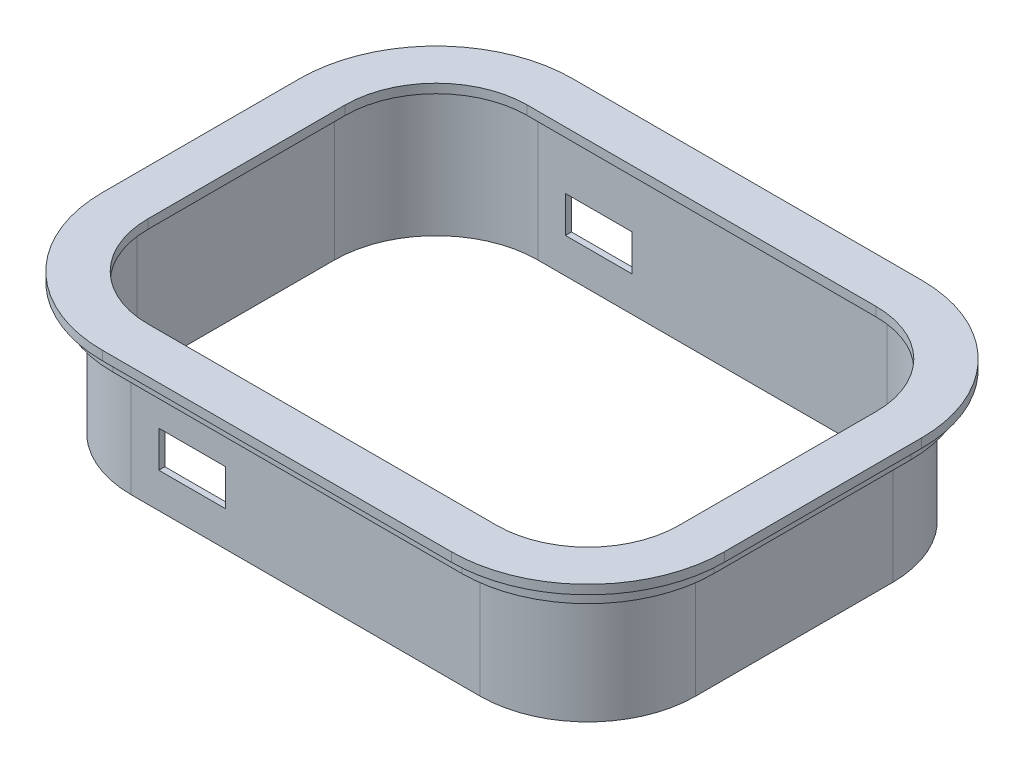
SolidWorks part; units mm, degrees
ref_plane "Front Plane" through (0, 0, 0) normal (0, 0, 1) x (1, 0, 0)
ref_plane "Top Plane" through (0, 0, 0) normal (0, 1, 0) x (1, 0, 0)
ref_plane "Right Plane" through (0, 0, 0) normal (1, 0, 0) x (0, 0, -1)
sketch "Sketch1" plane through (0, 0, 0) normal (0, 1, 0) x (1, 0, 0)
  line L0 (-57.5, 77.5) -> (57.5, 77.5)
  line L1 (-57.5, -62.5) -> (57.5, -62.5)
  line L2 (-87.5, -32.5) -> (-87.5, 32.5)
  line L3 (-57.5, 62.5) -> (57.5, 62.5)
  line L4 (87.5, -32.5) -> (87.5, 32.5)
  line L5 (-87.5, -62.5) -> (87.5, 62.5) construction
  line L6 (-87.5, 62.5) -> (87.5, -62.5) construction
  line L7 (102.5, -32.5) -> (102.5, 32.5)
  line L8 (-57.5, -77.5) -> (57.5, -77.5)
  line L9 (-102.5, -32.5) -> (-102.5, 32.5)
  line L10 (-57.5, 70) -> (57.5, 70) construction
  line L11 (95, -32.5) -> (95, 32.5) construction
  line L12 (-57.5, -70) -> (57.5, -70) construction
  line L13 (-95, -32.5) -> (-95, 32.5) construction
  line L14 (-57.5, 68) -> (57.5, 68)
  line L15 (93, -32.5) -> (93, 32.5)
  line L16 (-57.5, -68) -> (57.5, -68)
  line L17 (-93, -32.5) -> (-93, 32.5)
  line L18 (-57.5, 72) -> (57.5, 72)
  line L19 (97, -32.5) -> (97, 32.5)
  line L20 (-57.5, -72) -> (57.5, -72)
  line L21 (-97, -32.5) -> (-97, 32.5)
  line L22 (-57.5, 74) -> (57.5, 74)
  line L23 (99, -32.5) -> (99, 32.5)
  line L24 (-57.5, -74) -> (57.5, -74)
  line L25 (-99, -32.5) -> (-99, 32.5)
  line L26 (-57.5, 66) -> (57.5, 66)
  line L27 (91, -32.5) -> (91, 32.5)
  line L28 (-57.5, -66) -> (57.5, -66)
  line L29 (-91, -32.5) -> (-91, 32.5)
  arc A0 (57.5, -62.5) -> (87.5, -32.5) centre (57.5, -32.5) ccw
  arc A1 (-57.5, -62.5) -> (-87.5, -32.5) centre (-57.5, -32.5) cw
  arc A2 (57.5, 62.5) -> (87.5, 32.5) centre (57.5, 32.5) cw
  arc A3 (-87.5, 32.5) -> (-57.5, 62.5) centre (-57.5, 32.5) cw
  arc A4 (57.5, 77.5) -> (102.5, 32.5) centre (57.5, 32.5) cw
  arc A5 (57.5, -77.5) -> (102.5, -32.5) centre (57.5, -32.5) ccw
  arc A6 (-57.5, -77.5) -> (-102.5, -32.5) centre (-57.5, -32.5) cw
  arc A7 (-102.5, 32.5) -> (-57.5, 77.5) centre (-57.5, 32.5) cw
  arc A8 (57.5, 70) -> (95, 32.5) centre (57.5, 32.5) cw construction
  arc A9 (57.5, -70) -> (95, -32.5) centre (57.5, -32.5) ccw construction
  arc A10 (-57.5, -70) -> (-95, -32.5) centre (-57.5, -32.5) cw construction
  arc A11 (-95, 32.5) -> (-57.5, 70) centre (-57.5, 32.5) cw construction
  arc A12 (57.5, 68) -> (93, 32.5) centre (57.5, 32.5) cw
  arc A13 (57.5, -68) -> (93, -32.5) centre (57.5, -32.5) ccw
  arc A14 (-57.5, -68) -> (-93, -32.5) centre (-57.5, -32.5) cw
  arc A15 (-93, 32.5) -> (-57.5, 68) centre (-57.5, 32.5) cw
  arc A16 (57.5, 72) -> (97, 32.5) centre (57.5, 32.5) cw
  arc A17 (57.5, -72) -> (97, -32.5) centre (57.5, -32.5) ccw
  arc A18 (-57.5, -72) -> (-97, -32.5) centre (-57.5, -32.5) cw
  arc A19 (-97, 32.5) -> (-57.5, 72) centre (-57.5, 32.5) cw
  arc A20 (57.5, 74) -> (99, 32.5) centre (57.5, 32.5) cw
  arc A21 (57.5, -74) -> (99, -32.5) centre (57.5, -32.5) ccw
  arc A22 (-57.5, -74) -> (-99, -32.5) centre (-57.5, -32.5) cw
  arc A23 (-99, 32.5) -> (-57.5, 74) centre (-57.5, 32.5) cw
  arc A24 (57.5, 66) -> (91, 32.5) centre (57.5, 32.5) cw
  arc A25 (57.5, -66) -> (91, -32.5) centre (57.5, -32.5) ccw
  arc A26 (-57.5, -66) -> (-91, -32.5) centre (-57.5, -32.5) cw
  arc A27 (-91, 32.5) -> (-57.5, 66) centre (-57.5, 32.5) cw
  point P0 (0, 0)
  dimension "D3" = 30
  dimension "D1" = 175
  dimension "D2" = 125
  dimension "D4" = 15
  dimension "D5" = 7.5
  dimension "D6" = 2
  dimension "D7" = 2
  dimension "D8" = 2
  dimension "D9" = 2
extrude "Boss-Extrude1" add sketch "Sketch1" along normal blind 3 contours A15 L17 A14 L16 A13 L15 A12 L14 L2 A3 L3 A2 L4 A0 L1 A1 | A19 L21 A18 L20 A17 L19 A16 L18 L17 A15 L14 A12 L15 A13 L16 A14 | A23 L25 A22 L24 A21 L23 A20 L22 L21 A19 L18 A16 L19 A17 L20 A18 | A7 L9 A6 L8 A5 L7 A4 L0 L25 A23 L22 A20 L23 A21 L24 A22 | A27 L29 A26 L28 A25 L27 A24 L26 L2 A3 L3 A2 L4 A0 L1 A1 region at (0, 0, -74.93) region at (0, 0, -67.7696) region at (0, 0, -69.584) region at (0, 0, -73.7528) region at (0, 0, -63.7517)
extrude "Boss-Extrude2" add sketch "Sketch1<4>" against normal blind 5 contours A15 L17 A14 L16 A13 L15 A12 L14 L29 A27 L26 A24 L27 A25 L28 A26 | A23 L25 A22 L24 A21 L23 A20 L22 L21 A19 L18 A16 L19 A17 L20 A18 region at (0, 0, -67.7696) region at (0, 0, -73.7528)
sketch "Sketch1<4>" plane through (0, 0, 0) normal (0, 1, 0) x (1, 0, 0) same geometry as "Sketch1"
sketch "Sketch2" plane through (0, -5, 0) normal (0, -1, 0) x (1, 0, 0)
  line L0 (-91, 32.5) -> (-91, -32.5) construction
  line L1 (-57.5, -66) -> (57.5, -66) construction
  line L2 (91, 32.5) -> (91, -32.5) construction
  line L3 (-57.5, 66) -> (57.5, 66) construction
  line L4 (-57.5, -68) -> (57.5, -68)
  line L5 (93, -32.5) -> (93, 32.5)
  line L6 (57.5, 68) -> (-57.5, 68)
  line L7 (-93, 32.5) -> (-93, -32.5)
  line L8 (-57.5, -68) -> (57.5, -68)
  line L9 (93, -32.5) -> (93, 32.5)
  line L10 (57.5, 68) -> (-57.5, 68)
  line L11 (-93, 32.5) -> (-93, -32.5)
  line L12 (-91, 32.5) -> (-91, -32.5)
  line L13 (-57.5, -66) -> (57.5, -66)
  line L14 (91, 32.5) -> (91, -32.5)
  line L15 (-57.5, 66) -> (57.5, 66)
  arc A0 (-91, -32.5) -> (-57.5, -66) centre (-57.5, -32.5) ccw construction
  arc A1 (57.5, -66) -> (91, -32.5) centre (57.5, -32.5) ccw construction
  arc A2 (91, 32.5) -> (57.5, 66) centre (57.5, 32.5) ccw construction
  arc A3 (-57.5, 66) -> (-91, 32.5) centre (-57.5, 32.5) ccw construction
  arc A4 (-93, -32.5) -> (-57.5, -68) centre (-57.5, -32.5) ccw
  arc A5 (57.5, -68) -> (93, -32.5) centre (57.5, -32.5) ccw
  arc A6 (93, 32.5) -> (57.5, 68) centre (57.5, 32.5) ccw
  arc A7 (-57.5, 68) -> (-93, 32.5) centre (-57.5, 32.5) ccw
  arc A8 (-93, -32.5) -> (-57.5, -68) centre (-57.5, -32.5) ccw
  arc A9 (57.5, -68) -> (93, -32.5) centre (57.5, -32.5) ccw
  arc A10 (93, 32.5) -> (57.5, 68) centre (57.5, 32.5) ccw
  arc A11 (-57.5, 68) -> (-93, 32.5) centre (-57.5, 32.5) ccw
  arc A12 (-91, -32.5) -> (-57.5, -66) centre (-57.5, -32.5) ccw
  arc A13 (57.5, -66) -> (91, -32.5) centre (57.5, -32.5) ccw
  arc A14 (91, 32.5) -> (57.5, 66) centre (57.5, 32.5) ccw
  arc A15 (-57.5, 66) -> (-91, 32.5) centre (-57.5, 32.5) ccw
  dimension "D1" = 0
extrude "Boss-Extrude3" add sketch "Sketch2" along normal blind 38
sketch "Sketch4" plane through (0, 0, 68) normal (0, 0, 1) x (1, 0, 0)
  line L0 (-48.4005, -19.4481) -> (-26.4005, -19.4481)
  line L1 (-47.4005, -30.4481) -> (-27.4005, -30.4481)
  line L2 (-47.4005, -30.4481) -> (-47.4005, -20.4481)
  line L3 (-47.4005, -20.4481) -> (-27.4005, -20.4481)
  line L4 (-27.4005, -30.4481) -> (-27.4005, -20.4481)
  line L5 (-47.4005, -30.4481) -> (-27.4005, -20.4481) construction
  line L6 (-47.4005, -20.4481) -> (-27.4005, -30.4481) construction
  line L7 (-26.4005, -31.4481) -> (-26.4005, -19.4481)
  line L8 (-48.4005, -31.4481) -> (-26.4005, -31.4481)
  line L9 (-48.4005, -31.4481) -> (-48.4005, -19.4481)
  point P0 (-37.4005, -25.4481)
  dimension "D1" = 20
  dimension "D2" = 10
  dimension "D3" = 1
extrude "Cut-Extrude1" cut sketch "Sketch4" against normal blind 461 contours L1 L4 L3 L2 | L9 L8 L7 L0 L4 L1 L2 L3 region at (-37.4005, -19.6987, 68) region at (-37.4005, -25.4481, 68)
equation "\"Food_Width\"= 120"
equation "\"D1@Sketch1\"=\"Food_Length\"+\"Allowance\""
equation "\"Food_Length\"= 170"
equation "\"Allowance\"= 5"
equation "\"Inner Fillet\"= 10"
equation "\"D2@Sketch1\"=\"Food_Width\"+\"Allowance\""
equation "\"Frame_Width\"= 15"
equation "\"D4@Sketch1\"=\"Frame_Width\""
equation "\"D5@Sketch1\"=\"D4@Sketch1\"/2"
equation "\"CAM Thickness\"= 3"
equation "\"CAM Allowance\"= 0.5"
equation "\"D6@Sketch1\"=\"CAM Thickness\"/2+\"CAM Allowance\""
equation "\"D7@Sketch1\"=\"D6@Sketch1\""
equation "\"Wall_Thickness\"= 2"
equation "\"Frame_Thickness\"= 3"
equation "\"D8@Sketch1\"=\"Wall_Thickness\""
equation "\"D1@Boss-Extrude1\"=\"Frame_Thickness\""
equation "\"D9@Sketch1\"=\"Wall_Thickness\""
equation "\"Wall_Height\"= 5"
equation "\"D1@Boss-Extrude2\"=\"Wall_Height\""
equation "\"Inside_Wall_Height\" = 40"
equation "\"D1@Boss-Extrude3\" = \"Inside_Wall_Height\" - \"Wall_Thickness\""
